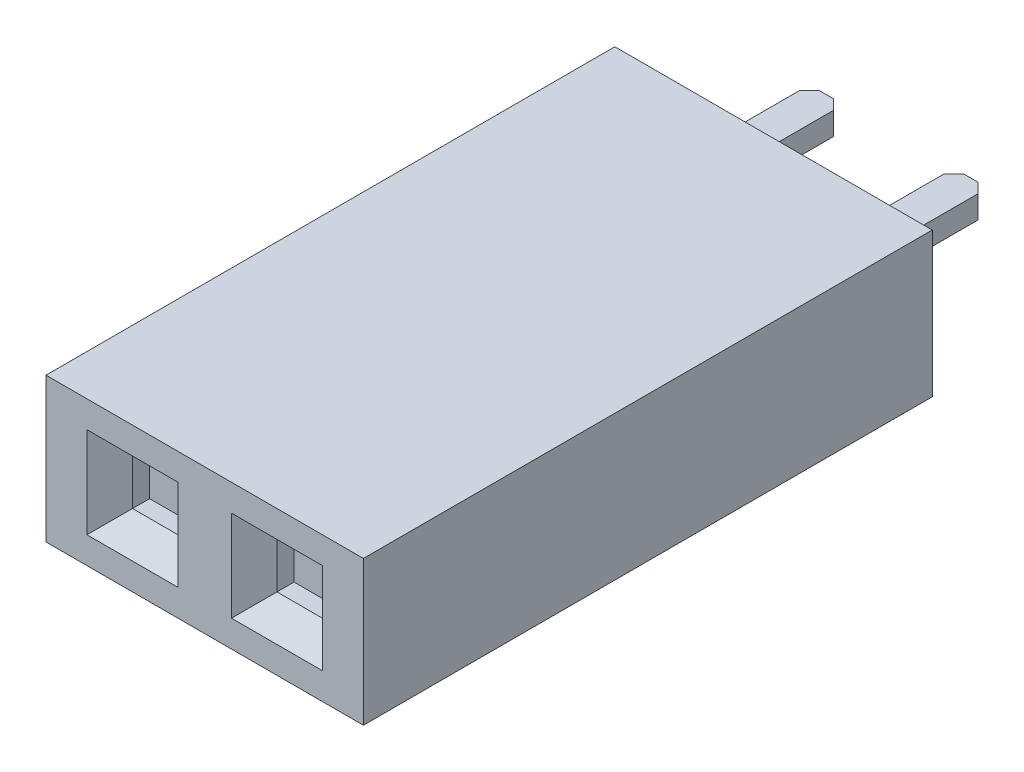
SolidWorks part; units mm, degrees
ref_plane "Front Plane" through (0, 0, 0) normal (0, 0, 1) x (1, 0, 0)
ref_plane "Top Plane" through (0, 0, 0) normal (0, 1, 0) x (1, 0, 0)
ref_plane "Right Plane" through (0, 0, 0) normal (1, 0, 0) x (0, 0, -1)
sketch "Sketch1" plane through (0, 0, 0) normal (1, 0, 0) x (0, -1, 0)
  line L1 (-1.27, 0) -> (1.27, 0)
  line L2 (-1.27, 0) -> (-1.27, -10)
  line L3 (-1.27, -10) -> (1.27, -10)
  line L4 (1.27, 0) -> (1.27, -10)
  line L5 (-1.27, 0) -> (1.27, -10) construction
  line L6 (-1.27, -10) -> (1.27, 0) construction
  point P0 (0, -5)
  point P6 (0, 0)
  dimension "D1" = 2.54
  dimension "D2" = 10
extrude "Boss-Extrude1" add sketch "Sketch1" along normal mid plane 3.04
sketch "Sketch2" plane through (0, 0, 10) normal (0, 0, 1) x (-1, 0, 0)
  line L0 (0, -1.27) -> (0, 1.27) construction
  line L3 (-1.52, -1.27) -> (1.52, -1.27) construction
  line L4 (-0.4, 0.4) -> (0.4, 0.4)
  line L5 (-0.4, 0.4) -> (-0.4, -0.4)
  line L6 (-0.4, -0.4) -> (0.4, -0.4)
  line L7 (0.4, 0.4) -> (0.4, -0.4)
  line L8 (-0.4, 0.4) -> (0.4, -0.4) construction
  line L9 (-0.4, -0.4) -> (0.4, 0.4) construction
  line L10 (-1.52, 1.27) -> (1.52, 1.27) construction
  point P5 (0, 0)
  dimension "D1" = 0.8
extrude "Cut-Extrude1" cut sketch "Sketch2" against normal blind 0.7
chamfer "Фаска1" distance 0.4 angle 45 4 edges at (-0.4, 0, 10) (0, -0.4, 10) (0.4, 0, 10) (0, 0.4, 10)
sketch "Sketch3" plane through (0, 0, 0) normal (0, 1, 0) x (1, 0, 0)
  line L0 (-0.3, 0) -> (-0.3, 2.0243)
  line L2 (-0.3, 2.0243) -> (-0.1243, 2.2)
  line L3 (-0.1243, 2.2) -> (0.1243, 2.2)
  line L4 (0, 2.2) -> (0, 0) construction
  line L5 (-0.3, 0) -> (0.3, 0)
  line L6 (0.3, 2.0243) -> (0.1243, 2.2)
  line L7 (0.3, 0) -> (0.3, 2.0243)
  dimension "D1" = 0.6
  dimension "D2" = 45
  dimension "D3" = 2.2
extrude "Boss-Extrude2" add sketch "Sketch3" along normal mid plane 0.4
pattern_linear "LPattern1" count 2 spacing 2.54 along (1, 0, 0) of bodies 103
combine bodies "Соединить1" operation type add bodies to combine 103 104
equation "\"0.4Aмм\"=0.45"
